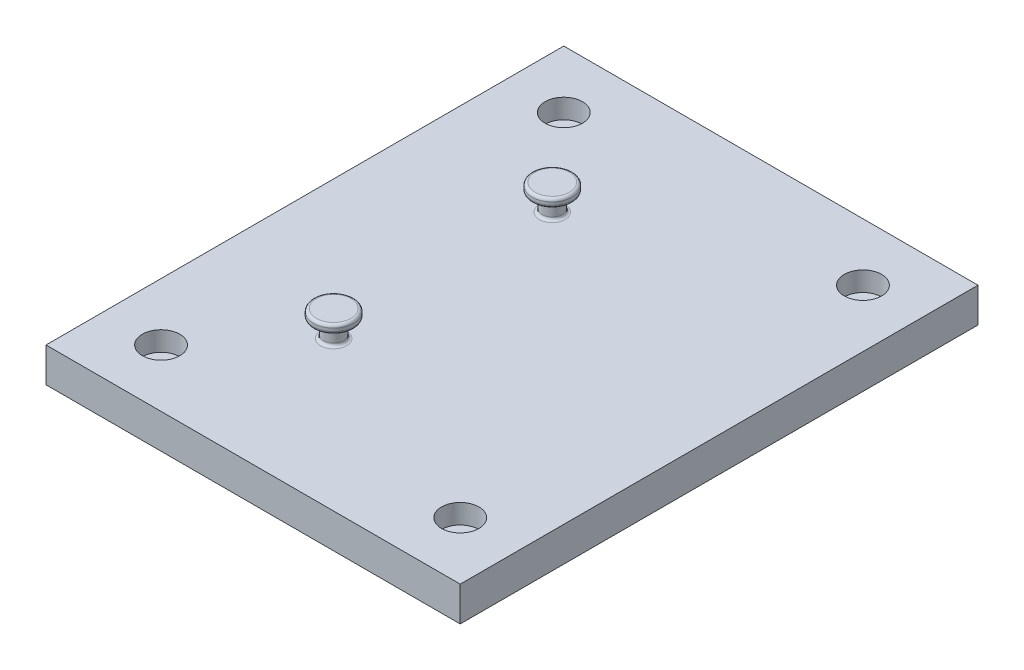
SolidWorks part; units mm, degrees
ref_plane "Front Plane" through (0, 0, 0) normal (0, 0, 1) x (1, 0, 0)
ref_plane "Top Plane" through (0, 0, 0) normal (0, 1, 0) x (1, 0, 0)
ref_plane "Right Plane" through (0, 0, 0) normal (1, 0, 0) x (0, 0, -1)
sketch "Szkic1" plane through (0, 0, 0) normal (0, 1, 0) x (1, 0, 0)
  line L0 (36, 45) -> (-36, -45) construction
  line L1 (-36, 45) -> (36, 45)
  line L2 (-36, 45) -> (-36, -45)
  line L3 (-36, -45) -> (36, -45)
  line L4 (36, 45) -> (36, -45)
  dimension "D1" = 72
  dimension "D2" = 90
extrude "Dodanie-wyciągnięcie1" add sketch "Szkic1" along normal blind 6
sketch "Szkic2" plane through (0, 6, 0) normal (0, 1, 0) x (1, 0, 0)
  line L0 (-36, 45) -> (-36, -45) construction
  line L1 (36, 45) -> (-36, 45) construction
  line L3 (-12, 19) -> (-12, 45) construction
  line L4 (-12, -19) -> (-12, -45) construction
  line L5 (-36, -45) -> (36, -45) construction
  circle A0 centre (-12, -19) radius 1.75
  circle A1 centre (-12, 19) radius 1.75
  circle A2 centre (-12, 19) radius 3.5
  circle A3 centre (-12, -19) radius 3.5
  dimension "D3" = 3.5
  dimension "D4" = 3.5
  dimension "D5" = 7
  dimension "D6" = 7
  dimension "D1" = 38
  dimension "D2" = 24
extrude "Dodanie-wyciągnięcie2" add sketch "Szkic2" along normal blind 3 contours A0 | A1 region at (-12, 6, 19) region at (-12, 6, -19)
extrude "Dodanie-wyciągnięcie3" add sketch "Szkic2<5>" along normal blind 1.5 from surface contours A3 | A2 starting at face at (-12, 9, 20.75)
sketch "Szkic2<5>" plane through (0, 6, 0) normal (0, 1, 0) x (1, 0, 0) same geometry as "Szkic2"
fillet "Zaokrąglenie1" radius 0.5 6 edges at (-12, 10.5, -15.5) (-12, 9, -15.5) (-12, 10.5, 22.5) (-12, 9, 22.5) (-12, 6, -17.25) (-12, 6, 20.75)
hole_wizard "CBORE for M3 Hex Socket Head Cap Screw1" positions "Szkic3" profile "Szkic4" counterbore size "M3" standard "DIN"
sketch "Szkic3" plane through (0, 6, 0) normal (0, 1, 0) x (1, 0, 0)
  line L0 (-26, 35) -> (-26, -35) construction
  line L2 (-26, 35) -> (26, 35) construction
  line L3 (26, 35) -> (26, -35) construction
  line L4 (26, -35) -> (-26, -35) construction
  line L6 (-36, 45) -> (-36, -45) construction
  line L7 (36, 45) -> (-36, 45) construction
  line L8 (-36, -45) -> (36, -45) construction
  line L10 (36, -45) -> (36, 45) construction
  point P0 (-26, 35)
  point P2 (26, 35)
  point P4 (26, -35)
  point P6 (-26, -35)
  dimension "D1" = 10
  dimension "D2" = 10
  dimension "D3" = 10
  dimension "D4" = 10
sketch "Szkic4" plane through (-26, 6, -35) normal (1, 0, 0) x (0, 0, 1)
  line L0 (0, 0) -> (0, 8.6614)
  line L1 (0, 8.6614) -> (1.6, 7.7)
  line L2 (1.6, 7.7) -> (1.6, 3.4)
  line L3 (1.6, 3.4) -> (3.25, 3.4)
  line L4 (3.25, 3.4) -> (3.25, 0)
  line L5 (3.25, 0) -> (0, 0)
  line L10 (0, 8.6614) -> (-1.6, 7.7) construction
  line L11 (0, -6.35) -> (0, 107.95) construction
  dimension "Hole Dia." = 3.2
  dimension "Hole Depth" = 7.7
  dimension "C'Bore Dia." = 6.5
  dimension "C'Bore Depth" = 3.4
  dimension "Drill Angle" = 118
